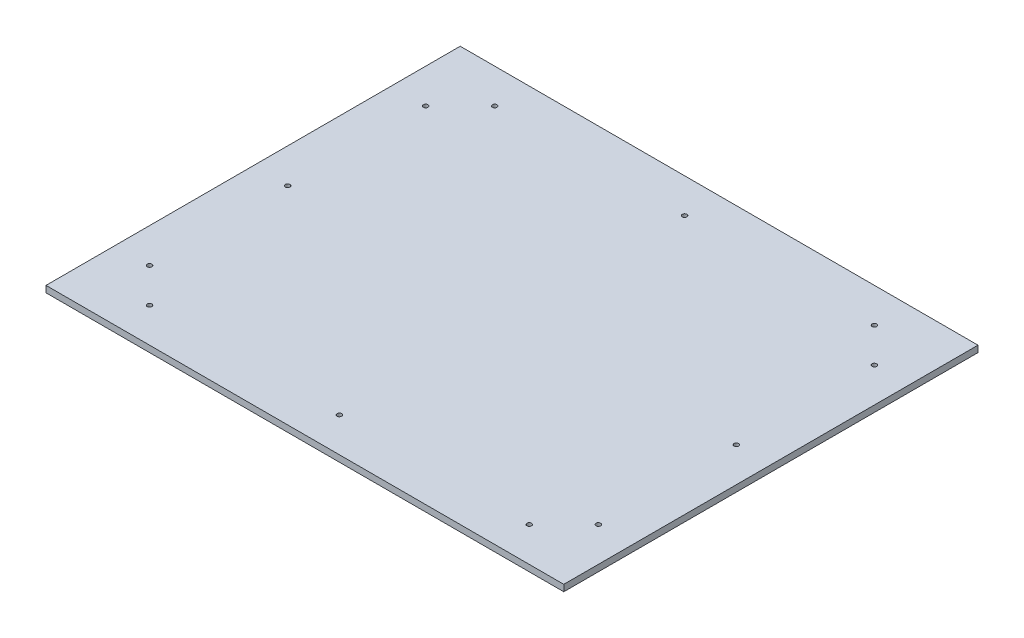
SolidWorks part; units mm, degrees
material "6061 Alloy"
ref_plane "Front Plane" through (0, 0, 0) normal (0, 0, 1) x (1, 0, 0)
ref_plane "Top Plane" through (0, 0, 0) normal (0, 1, 0) x (1, 0, 0)
ref_plane "Right Plane" through (0, 0, 0) normal (1, 0, 0) x (0, 0, -1)
sketch "Sketch1" plane through (0, 0, 0) normal (0, 1, 0) x (1, 0, 0)
  line L1 (-190.5, -152.4) -> (190.5, -152.4)
  line L2 (-190.5, -152.4) -> (-190.5, 152.4)
  line L3 (-190.5, 152.4) -> (190.5, 152.4)
  line L4 (190.5, -152.4) -> (190.5, 152.4)
  line L5 (-190.5, -152.4) -> (190.5, 152.4) construction
  line L6 (-190.5, 152.4) -> (190.5, -152.4) construction
  point P0 (0, 0)
  dimension "D1" = 304.8
  dimension "D2" = 381
extrude "Boss-Extrude1" add sketch "Sketch1" along normal blind 4.7625
sketch "Sketch2" plane through (0, 4.7625, 0) normal (0, 1, 0) x (1, 0, 0)
  line L0 (-165.1, 152.4) -> (-165.1, -152.4) construction
  line L1 (190.5, 152.4) -> (-190.5, 152.4) construction
  line L2 (-190.5, -152.4) -> (190.5, -152.4) construction
  line L3 (-190.5, -127) -> (190.5, -127) construction
  line L4 (-190.5, 152.4) -> (-190.5, -152.4) construction
  line L5 (190.5, -152.4) -> (190.5, 152.4) construction
  line L6 (-190.5, 127) -> (190.5, 127) construction
  line L7 (165.1, 152.4) -> (165.1, -152.4) construction
  point P16 (-165.1, 0)
  point P17 (0, -127)
  point P18 (165.1, 0)
  point P19 (0, 127)
  point P20 (-165.1, 101.6)
  point P21 (-165.1, -101.6)
  point P22 (-139.7, 127)
  point P23 (-139.7, -127)
  point P24 (139.7, 127)
  point P25 (139.7, -127)
  point P26 (165.1, 101.6)
  point P27 (165.1, -101.6)
  point P28 (0, 0)
  point P29 (0, 0)
  point P30 (0, 0)
  point P31 (0, 0)
  dimension "D1" = 25.4
  dimension "D2" = 25.4
  dimension "D3" = 25.4
  dimension "D4" = 25.4
  dimension "D5" = 50.8
  dimension "D6" = 50.8
  dimension "D7" = 50.8
  dimension "D8" = 50.8
hole_wizard "M3 Clearance Hole1" positions "3DSketch1" profile "Sketch3" hole size "M3" standard "ANSI Metric" end condition through all
sketch3d "3DSketch1"
  point P0 (-165.1, 4.7625, 101.6)
  point P3 (-165.1, 4.7625, 0)
  point P10 (-165.1, 4.7625, -101.6)
  point P13 (-139.7, 4.7625, -127)
  point P16 (0, 4.7625, -127)
  point P19 (139.7, 4.7625, -127)
  point P22 (165.1, 4.7625, -101.6)
  point P25 (165.1, 4.7625, 0)
  point P28 (165.1, 4.7625, 101.6)
  point P31 (139.7, 4.7625, 127)
  point P34 (0, 4.7625, 127)
  point P37 (-139.7, 4.7625, 127)
sketch "Sketch3" plane through (-165.1, 4.7625, 101.6) normal (1, 0, 0) x (0, 0, 1)
  line L0 (0, 0) -> (0, 4.7625)
  line L1 (0, 4.7625) -> (1.7, 4.7625)
  line L2 (1.7, 4.7625) -> (1.7, 0)
  line L5 (1.7, 0) -> (0, 0)
  line L11 (0, -6.35) -> (0, 107.95) construction
  dimension "Thru Hole Dia." = 3.4
  dimension "Thru Hole Depth" = 4.7625
equation "\"D3@Sketch2\"=\"D1@Sketch2\""
equation "\"D4@Sketch2\"=\"D2@Sketch2\""
equation "\"D6@Sketch2\"=\"D5@Sketch2\""
equation "\"D7@Sketch2\"=\"D5@Sketch2\""
equation "\"D8@Sketch2\"=\"D5@Sketch2\""
